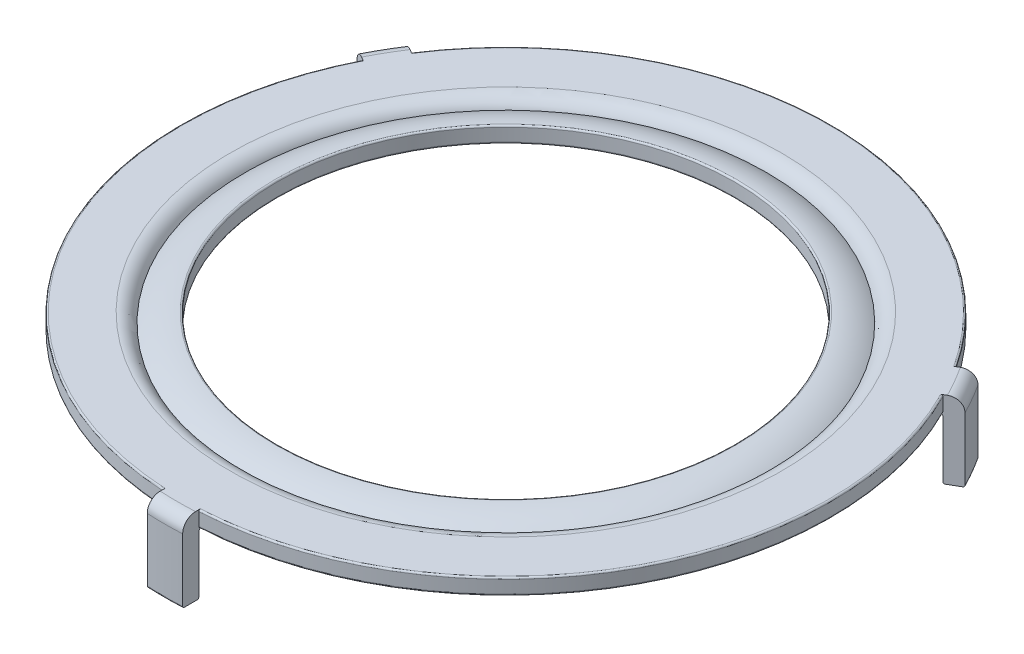
SolidWorks part; units mm, degrees
ref_plane "Plano frontal" through (0, 0, 0) normal (0, 0, 1) x (1, 0, 0)
ref_plane "Plano superior" through (0, 0, 0) normal (0, 1, 0) x (1, 0, 0)
ref_plane "Plano direito" through (0, 0, 0) normal (1, 0, 0) x (0, 0, -1)
sketch "Esboço1" plane through (0, 0, 0) normal (0, 0, 1) x (1, 0, 0)
  line L0 (0, -40.0479) -> (0, 43.8734) construction
  line L1 (50.5, 2.1156) -> (50.5, 4.6156)
  line L2 (50.5, 4.6156) -> (42.7913, 4.6156)
  line L3 (35.5, 4.6156) -> (35.5, 2.1156)
  line L4 (35.5, 2.1156) -> (38.5, 2.1156)
  line L5 (50.5, 2.1156) -> (44.25, 2.1156)
  arc A0 (42.7913, 4.6156) -> (40.5, 3.1156) centre (42.7913, 2.1156) ccw
  arc A1 (40.5, 3.1156) -> (35.5, 4.6156) centre (35.4816, -4.5289) ccw
  arc A2 (38.5, 2.1156) -> (44.25, 2.1156) centre (41.375, 4.8967) ccw
  dimension "D9" = 4
  dimension "D11" = 2.5
  dimension "D1" = 35.5
  dimension "D2" = 38.5
  dimension "D3" = 40.5
  dimension "D4" = 44.25
  dimension "D5" = 50.5
  dimension "D6" = 2.5
  dimension "D7" = 2.5
  dimension "D8" = 1.5
  dimension "D10" = 0
revolve "Revolução2" add sketch "Esboço1" angle 360 about L0
sketch "Esboço2" plane through (0, 4.6156, 0) normal (0, 1, 0) x (1, 0, 0)
  line L0 (-2.75, 0) -> (2.75, 0)
  line L1 (-2.75, -52.9286) -> (-2.75, -50.4251)
  line L2 (2.75, -52.9286) -> (2.75, -50.4251)
  line L3 (-44.4625, 28.8459) -> (-42.2944, 27.5941)
  line L4 (-47.2125, 24.0827) -> (-45.0444, 22.831)
  line L5 (47.2125, 24.0827) -> (45.0444, 22.831)
  line L6 (44.4625, 28.8459) -> (42.2944, 27.5941)
  arc A1 (-44.4625, 28.8459) -> (-47.2125, 24.0827) centre (0, 0) ccw
  arc A2 (-2.75, -52.9286) -> (2.75, -52.9286) centre (0, 0) ccw
  arc A3 (-2.75, -50.4251) -> (2.75, -50.4251) centre (0, 0) ccw
  arc A4 (-42.2944, 27.5941) -> (-45.0444, 22.831) centre (0, 0) ccw
  arc A5 (47.2125, 24.0827) -> (44.4625, 28.8459) centre (0, 0) ccw
  arc A6 (45.0444, 22.831) -> (42.2944, 27.5941) centre (0, 0) ccw
  point P20 (0, 0)
  circle M2 centre (0, 0) radius 50.5
  dimension "D1" = 3
extrude "Ressalto-extrusão1" add sketch "Esboço2" against normal blind 12 contours L3 A1 L4 M2 | L5 A5 L6 M2 | L1 A2 L2 M2 region at (0, 4.6156, 51.7256) region at (-44.7957, 4.6156, -25.8628) region at (44.7957, 4.6156, -25.8628)
fillet "Filete1" radius 2 3 edges at (0, 4.6156, 53) (45.8993, 4.6156, -26.5) (-45.8993, 4.6156, -26.5)
fillet "Filete2" radius 0.25 6 edges at (0, -7.3844, 53) (0, -7.3844, 50.5) (-45.8993, -7.3844, -26.5) (-43.7343, -7.3844, -25.25) (43.7343, -7.3844, -25.25) (45.8993, -7.3844, -26.5)
fillet "Filete3" radius 0.5 3 edges at (-43.7343, 2.1156, -25.25) (43.7343, 2.1156, -25.25) (0, 2.1156, 50.5)
fillet "Filete4" radius 0.25 8 edges at (0, 2.1156, -35.5) (-43.7343, 4.6156, 25.25) (43.7343, 4.6156, 25.25) (43.7343, 2.1156, 25.25) (-43.7343, 2.1156, 25.25) (0, 2.1156, -50.5) (0, 4.6156, -50.5) (0, 4.6156, -35.5)
